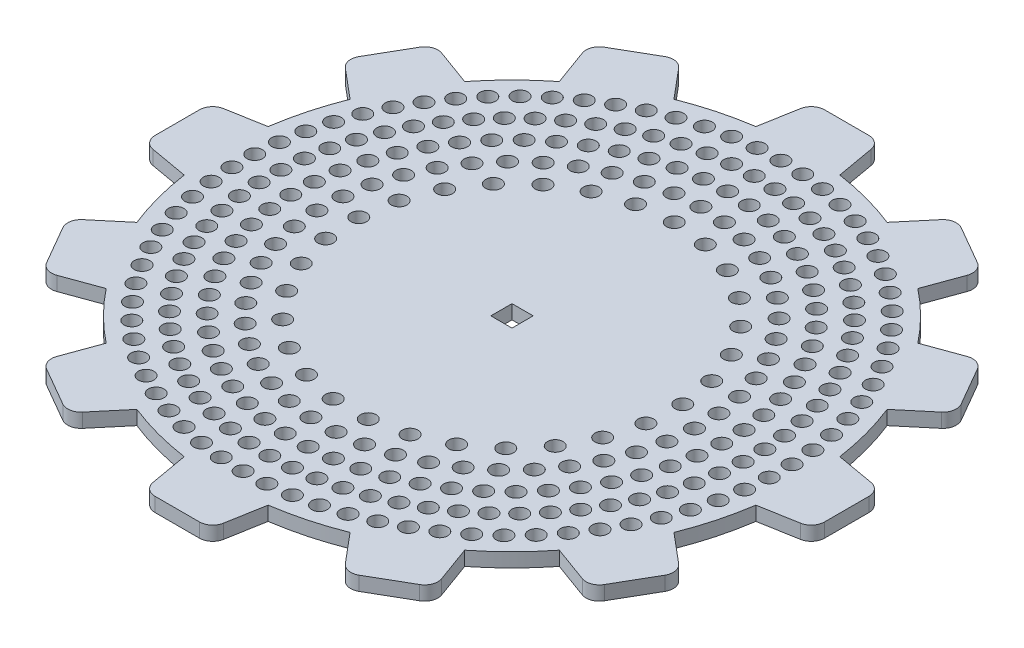
SolidWorks part; units mm, degrees
material "Balsa"
ref_plane "Front Plane" through (0, 0, 0) normal (0, 0, 1) x (1, 0, 0)
ref_plane "Top Plane" through (0, 0, 0) normal (0, 1, 0) x (1, 0, 0)
ref_plane "Right Plane" through (0, 0, 0) normal (1, 0, 0) x (0, 0, -1)
sketch "Sketch1" plane through (0, 0, 0) normal (0, 1, 0) x (1, 0, 0)
  line L0 (0, 85) -> (0, 73) construction
  line L1 (-4.7625, 4.7625) -> (4.7625, 4.7625)
  line L2 (-4.7625, 4.7625) -> (-4.7625, -4.7625)
  line L7 (-4.7625, -4.7625) -> (4.7625, -4.7625)
  line L8 (0, 121) -> (0, 109) construction
  line L9 (0, 109) -> (0, 97) construction
  line L10 (0, 97) -> (0, 85) construction
  line L11 (4.7625, 4.7625) -> (4.7625, -4.7625)
  line L12 (-4.7625, 4.7625) -> (4.7625, -4.7625) construction
  line L13 (-4.7625, -4.7625) -> (4.7625, 4.7625) construction
  circle A0 centre (0, 0) radius 130
  circle A39 centre (0, 85) radius 3.5
  circle A40 centre (0, 97) radius 3.5
  circle A41 centre (0, 109) radius 3.5
  circle A42 centre (0, 121) radius 3.5
  circle A43 centre (10.2615, 120.5641) radius 3.5
  circle A44 centre (20.4491, 119.2595) radius 3.5
  circle A45 centre (30.4893, 117.0957) radius 3.5
  circle A46 centre (40.3099, 114.0882) radius 3.5
  circle A47 centre (49.8401, 110.2586) radius 3.5
  circle A48 centre (59.0111, 105.6347) radius 3.5
  circle A49 centre (67.7569, 100.2497) radius 3.5
  circle A50 centre (76.0146, 94.1423) radius 3.5
  circle A51 centre (83.7246, 87.3567) radius 3.5
  circle A52 centre (90.8313, 79.9416) radius 3.5
  circle A53 centre (97.2837, 71.9506) radius 3.5
  circle A54 centre (103.035, 63.4412) radius 3.5
  circle A55 centre (108.044, 54.4747) radius 3.5
  circle A56 centre (112.2746, 45.1156) radius 3.5
  circle A57 centre (115.6962, 35.4316) radius 3.5
  circle A58 centre (118.2842, 25.4922) radius 3.5
  circle A59 centre (120.02, 15.3692) radius 3.5
  circle A60 centre (120.891, 5.1354) radius 3.5
  circle A61 centre (120.891, -5.1354) radius 3.5
  circle A62 centre (120.02, -15.3692) radius 3.5
  circle A63 centre (118.2842, -25.4922) radius 3.5
  circle A64 centre (115.6962, -35.4316) radius 3.5
  circle A65 centre (112.2746, -45.1156) radius 3.5
  circle A66 centre (108.044, -54.4747) radius 3.5
  circle A67 centre (103.035, -63.4412) radius 3.5
  circle A68 centre (97.2837, -71.9506) radius 3.5
  circle A69 centre (90.8313, -79.9416) radius 3.5
  circle A70 centre (83.7246, -87.3567) radius 3.5
  circle A71 centre (76.0146, -94.1423) radius 3.5
  circle A72 centre (67.7569, -100.2497) radius 3.5
  circle A73 centre (59.0111, -105.6347) radius 3.5
  circle A74 centre (49.8401, -110.2586) radius 3.5
  circle A75 centre (40.3099, -114.0882) radius 3.5
  circle A76 centre (30.4893, -117.0957) radius 3.5
  circle A77 centre (20.4491, -119.2595) radius 3.5
  circle A78 centre (10.2615, -120.5641) radius 3.5
  circle A79 centre (0, -121) radius 3.5
  circle A80 centre (-10.2615, -120.5641) radius 3.5
  circle A81 centre (-20.4491, -119.2595) radius 3.5
  circle A82 centre (-30.4893, -117.0957) radius 3.5
  circle A83 centre (-40.3099, -114.0882) radius 3.5
  circle A84 centre (-49.8401, -110.2586) radius 3.5
  circle A85 centre (-59.0111, -105.6347) radius 3.5
  circle A86 centre (-67.7569, -100.2497) radius 3.5
  circle A87 centre (-76.0146, -94.1423) radius 3.5
  circle A88 centre (-83.7246, -87.3567) radius 3.5
  circle A89 centre (-90.8313, -79.9416) radius 3.5
  circle A90 centre (-97.2837, -71.9506) radius 3.5
  circle A91 centre (-103.035, -63.4412) radius 3.5
  circle A92 centre (-108.044, -54.4747) radius 3.5
  circle A93 centre (-112.2746, -45.1156) radius 3.5
  circle A94 centre (-115.6962, -35.4316) radius 3.5
  circle A95 centre (-118.2842, -25.4922) radius 3.5
  circle A96 centre (-120.02, -15.3692) radius 3.5
  circle A97 centre (-120.891, -5.1354) radius 3.5
  circle A98 centre (-120.891, 5.1354) radius 3.5
  circle A99 centre (-120.02, 15.3692) radius 3.5
  circle A100 centre (-118.2842, 25.4922) radius 3.5
  circle A101 centre (-115.6962, 35.4316) radius 3.5
  circle A102 centre (-112.2746, 45.1156) radius 3.5
  circle A103 centre (-108.044, 54.4747) radius 3.5
  circle A104 centre (-103.035, 63.4412) radius 3.5
  circle A105 centre (-97.2837, 71.9506) radius 3.5
  circle A106 centre (-90.8313, 79.9416) radius 3.5
  circle A107 centre (-83.7246, 87.3567) radius 3.5
  circle A108 centre (9.7707, 108.5612) radius 3.5
  circle A109 centre (19.4627, 107.2483) radius 3.5
  circle A110 centre (28.998, 105.072) radius 3.5
  circle A111 centre (38.2999, 102.0496) radius 3.5
  circle A112 centre (47.2933, 98.2056) radius 3.5
  circle A113 centre (55.906, 93.5709) radius 3.5
  circle A114 centre (64.0686, 88.1829) radius 3.5
  circle A115 centre (71.7153, 82.0848) radius 3.5
  circle A116 centre (78.7846, 75.3258) radius 3.5
  circle A117 centre (85.2196, 67.9604) radius 3.5
  circle A118 centre (90.9685, 60.0478) radius 3.5
  circle A119 centre (95.9849, 51.6517) radius 3.5
  circle A120 centre (100.2285, 42.8397) radius 3.5
  circle A121 centre (103.6652, 33.6829) radius 3.5
  circle A122 centre (106.2671, 24.2548) radius 3.5
  circle A123 centre (108.0135, 14.6314) radius 3.5
  circle A124 centre (108.8902, 4.8903) radius 3.5
  circle A125 centre (108.8902, -4.8903) radius 3.5
  circle A126 centre (108.0135, -14.6314) radius 3.5
  circle A127 centre (106.2671, -24.2548) radius 3.5
  circle A128 centre (103.6652, -33.6829) radius 3.5
  circle A129 centre (100.2285, -42.8397) radius 3.5
  circle A130 centre (95.9849, -51.6517) radius 3.5
  circle A131 centre (90.9685, -60.0478) radius 3.5
  circle A132 centre (85.2196, -67.9604) radius 3.5
  circle A133 centre (78.7846, -75.3258) radius 3.5
  circle A134 centre (71.7153, -82.0848) radius 3.5
  circle A135 centre (64.0686, -88.1829) radius 3.5
  circle A136 centre (55.906, -93.5709) radius 3.5
  circle A137 centre (47.2933, -98.2056) radius 3.5
  circle A138 centre (38.2999, -102.0496) radius 3.5
  circle A139 centre (28.998, -105.072) radius 3.5
  circle A140 centre (19.4627, -107.2483) radius 3.5
  circle A141 centre (9.7707, -108.5612) radius 3.5
  circle A142 centre (0, -109) radius 3.5
  circle A143 centre (-9.7707, -108.5612) radius 3.5
  circle A144 centre (-19.4627, -107.2483) radius 3.5
  circle A145 centre (-28.998, -105.072) radius 3.5
  circle A146 centre (-38.2999, -102.0496) radius 3.5
  circle A147 centre (-47.2933, -98.2056) radius 3.5
  circle A148 centre (-55.906, -93.5709) radius 3.5
  circle A149 centre (-64.0686, -88.1829) radius 3.5
  circle A150 centre (-71.7153, -82.0848) radius 3.5
  circle A151 centre (-78.7846, -75.3258) radius 3.5
  circle A152 centre (-85.2196, -67.9604) radius 3.5
  circle A153 centre (-90.9685, -60.0478) radius 3.5
  circle A154 centre (-95.9849, -51.6517) radius 3.5
  circle A155 centre (-100.2285, -42.8397) radius 3.5
  circle A156 centre (-103.6652, -33.6829) radius 3.5
  circle A157 centre (-106.2671, -24.2548) radius 3.5
  circle A158 centre (-108.0135, -14.6314) radius 3.5
  circle A159 centre (-108.8902, -4.8903) radius 3.5
  circle A160 centre (-108.8902, 4.8903) radius 3.5
  circle A161 centre (-108.0135, 14.6314) radius 3.5
  circle A162 centre (10.3105, 96.4505) radius 3.5
  circle A163 centre (20.5041, 94.8081) radius 3.5
  circle A164 centre (30.4654, 92.0916) radius 3.5
  circle A165 centre (40.0816, 88.3316) radius 3.5
  circle A166 centre (49.2436, 83.5707) radius 3.5
  circle A167 centre (57.8476, 77.863) radius 3.5
  circle A168 centre (65.7962, 71.2731) radius 3.5
  circle A169 centre (72.9994, 63.8756) radius 3.5
  circle A170 centre (79.3754, 55.7544) radius 3.5
  circle A171 centre (84.852, 47.0014) radius 3.5
  circle A172 centre (89.3673, 37.7159) radius 3.5
  circle A173 centre (92.8699, 28.0031) radius 3.5
  circle A174 centre (95.3204, 17.973) radius 3.5
  circle A175 centre (96.6908, 7.7393) radius 3.5
  circle A176 centre (96.9656, -2.5822) radius 3.5
  circle A177 centre (96.1418, -12.8744) radius 3.5
  circle A178 centre (94.2287, -23.0207) radius 3.5
  circle A179 centre (91.2479, -32.9062) radius 3.5
  circle A180 centre (87.2333, -42.4188) radius 3.5
  circle A181 centre (82.2302, -51.4508) radius 3.5
  circle A182 centre (76.2955, -59.8999) radius 3.5
  circle A183 centre (69.4963, -67.6703) radius 3.5
  circle A184 centre (61.9097, -74.6739) radius 3.5
  circle A185 centre (53.6216, -80.8315) radius 3.5
  circle A186 centre (44.726, -86.0732) radius 3.5
  circle A187 centre (35.3236, -90.3396) radius 3.5
  circle A188 centre (25.5209, -93.5825) radius 3.5
  circle A189 centre (15.4292, -95.765) radius 3.5
  circle A190 centre (5.1626, -96.8625) radius 3.5
  circle A191 centre (-5.1626, -96.8625) radius 3.5
  circle A192 centre (-15.4292, -95.765) radius 3.5
  circle A193 centre (-25.5209, -93.5825) radius 3.5
  circle A194 centre (-35.3236, -90.3396) radius 3.5
  circle A195 centre (-44.726, -86.0732) radius 3.5
  circle A196 centre (-53.6216, -80.8315) radius 3.5
  circle A197 centre (-61.9097, -74.6739) radius 3.5
  circle A198 centre (-69.4963, -67.6703) radius 3.5
  circle A199 centre (-76.2955, -59.8999) radius 3.5
  circle A200 centre (-82.2302, -51.4508) radius 3.5
  circle A201 centre (-87.2333, -42.4188) radius 3.5
  circle A202 centre (-91.2479, -32.9062) radius 3.5
  circle A203 centre (-94.2287, -23.0207) radius 3.5
  circle A204 centre (-96.1418, -12.8744) radius 3.5
  circle A205 centre (-96.9656, -2.5822) radius 3.5
  circle A206 centre (-96.6908, 7.7393) radius 3.5
  circle A207 centre (-95.3204, 17.973) radius 3.5
  circle A208 centre (-92.8699, 28.0031) radius 3.5
  circle A209 centre (-89.3673, 37.7159) radius 3.5
  circle A210 centre (-84.852, 47.0014) radius 3.5
  circle A211 centre (-79.3754, 55.7544) radius 3.5
  circle A212 centre (-72.9994, 63.8756) radius 3.5
  circle A214 centre (11.3294, 84.2416) radius 3.5
  circle A215 centre (22.4566, 81.9799) radius 3.5
  circle A216 centre (33.1831, 78.2552) radius 3.5
  circle A217 centre (43.3174, 73.1341) radius 3.5
  circle A218 centre (52.6787, 66.7079) radius 3.5
  circle A219 centre (61.1, 59.0914) radius 3.5
  circle A220 centre (68.431, 50.4203) radius 3.5
  circle A221 centre (74.5407, 40.8494) radius 3.5
  circle A222 centre (79.3204, 30.5497) radius 3.5
  circle A223 centre (82.6845, 19.7047) radius 3.5
  circle A224 centre (84.5731, 8.5081) radius 3.5
  circle A225 centre (84.9525, -2.8403) radius 3.5
  circle A226 centre (83.816, -14.138) radius 3.5
  circle A227 centre (81.1837, -25.1834) radius 3.5
  circle A228 centre (77.1027, -35.7795) radius 3.5
  circle A229 centre (71.6458, -45.737) radius 3.5
  circle A230 centre (64.9104, -54.8784) radius 3.5
  circle A231 centre (57.0167, -63.0404) radius 3.5
  circle A232 centre (48.1055, -70.0775) radius 3.5
  circle A233 centre (38.3359, -75.8641) radius 3.5
  circle A234 centre (27.8821, -80.2969) radius 3.5
  circle A235 centre (16.9308, -83.2967) radius 3.5
  circle A236 centre (5.6774, -84.8102) radius 3.5
  circle A237 centre (-5.6774, -84.8102) radius 3.5
  circle A238 centre (-16.9308, -83.2967) radius 3.5
  circle A239 centre (-27.8821, -80.2969) radius 3.5
  circle A240 centre (-38.3359, -75.8641) radius 3.5
  circle A241 centre (-48.1055, -70.0775) radius 3.5
  circle A242 centre (-57.0167, -63.0404) radius 3.5
  circle A243 centre (-64.9104, -54.8784) radius 3.5
  circle A244 centre (-71.6458, -45.737) radius 3.5
  circle A245 centre (-77.1027, -35.7795) radius 3.5
  circle A246 centre (-81.1837, -25.1834) radius 3.5
  circle A247 centre (-83.816, -14.138) radius 3.5
  circle A248 centre (-84.9525, -2.8403) radius 3.5
  circle A249 centre (-84.5731, 8.5081) radius 3.5
  circle A250 centre (-82.6845, 19.7047) radius 3.5
  circle A251 centre (-79.3204, 30.5497) radius 3.5
  circle A252 centre (-74.5407, 40.8494) radius 3.5
  circle A253 centre (-68.431, 50.4203) radius 3.5
  circle A254 centre (-61.1, 59.0914) radius 3.5
  circle A255 centre (-52.6787, 66.7079) radius 3.5
  circle A256 centre (-43.3174, 73.1341) radius 3.5
  circle A257 centre (-33.1831, 78.2552) radius 3.5
  circle A258 centre (-22.4566, 81.9799) radius 3.5
  circle A259 centre (-11.3294, 84.2416) radius 3.5
  circle A260 centre (-65.7962, 71.2731) radius 3.5
  circle A261 centre (-57.8476, 77.863) radius 3.5
  circle A262 centre (-49.2436, 83.5707) radius 3.5
  circle A263 centre (-40.0816, 88.3316) radius 3.5
  circle A264 centre (-30.4654, 92.0916) radius 3.5
  circle A265 centre (-20.5041, 94.8081) radius 3.5
  circle A266 centre (-10.3105, 96.4505) radius 3.5
  circle A267 centre (-106.2671, 24.2548) radius 3.5
  circle A268 centre (-103.6652, 33.6829) radius 3.5
  circle A269 centre (-100.2285, 42.8397) radius 3.5
  circle A270 centre (-95.9849, 51.6517) radius 3.5
  circle A271 centre (-90.9685, 60.0478) radius 3.5
  circle A272 centre (-85.2196, 67.9604) radius 3.5
  circle A273 centre (-78.7846, 75.3258) radius 3.5
  circle A274 centre (-71.7153, 82.0848) radius 3.5
  circle A275 centre (-64.0686, 88.1829) radius 3.5
  circle A276 centre (-55.906, 93.5709) radius 3.5
  circle A277 centre (-47.2933, 98.2056) radius 3.5
  circle A278 centre (-38.2999, 102.0496) radius 3.5
  circle A279 centre (-28.998, 105.072) radius 3.5
  circle A280 centre (-19.4627, 107.2483) radius 3.5
  circle A281 centre (-9.7707, 108.5612) radius 3.5
  circle A282 centre (-76.0146, 94.1423) radius 3.5
  circle A283 centre (-67.7569, 100.2497) radius 3.5
  circle A284 centre (-59.0111, 105.6347) radius 3.5
  circle A285 centre (-49.8401, 110.2586) radius 3.5
  circle A286 centre (-40.3099, 114.0882) radius 3.5
  circle A287 centre (-30.4893, 117.0957) radius 3.5
  circle A288 centre (-20.4491, 119.2595) radius 3.5
  circle A289 centre (-10.2615, 120.5641) radius 3.5
  circle A290 centre (0, 73) radius 3.5
  circle A291 centre (15.6928, 71.2933) radius 3.5
  circle A292 centre (30.6519, 66.253) radius 3.5
  circle A293 centre (44.1777, 58.1148) radius 3.5
  circle A294 centre (55.6378, 47.2592) radius 3.5
  circle A295 centre (64.4964, 34.1938) radius 3.5
  circle A296 centre (70.3391, 19.5296) radius 3.5
  circle A297 centre (72.8929, 3.9521) radius 3.5
  circle A298 centre (72.0383, -11.8101) radius 3.5
  circle A299 centre (67.8153, -27.0201) radius 3.5
  circle A300 centre (60.4213, -40.9667) radius 3.5
  circle A301 centre (50.2021, -52.9977) radius 3.5
  circle A302 centre (37.6354, -62.5506) radius 3.5
  circle A303 centre (23.309, -69.1787) radius 3.5
  circle A304 centre (7.8927, -72.5721) radius 3.5
  circle A305 centre (-7.8927, -72.5721) radius 3.5
  circle A306 centre (-23.309, -69.1787) radius 3.5
  circle A307 centre (-37.6354, -62.5506) radius 3.5
  circle A308 centre (-50.2021, -52.9977) radius 3.5
  circle A309 centre (-60.4213, -40.9667) radius 3.5
  circle A310 centre (-67.8153, -27.0201) radius 3.5
  circle A311 centre (-72.0383, -11.8101) radius 3.5
  circle A312 centre (-72.8929, 3.9521) radius 3.5
  circle A313 centre (-70.3391, 19.5296) radius 3.5
  circle A314 centre (-64.4964, 34.1938) radius 3.5
  circle A315 centre (-55.6378, 47.2592) radius 3.5
  circle A316 centre (-44.1777, 58.1148) radius 3.5
  circle A317 centre (-30.6519, 66.253) radius 3.5
  circle A318 centre (-15.6928, 71.2933) radius 3.5
  point P568 (0, 0)
  dimension "D2" = 12
  dimension "D3" = 260
  dimension "D4" = 85
  dimension "D12" = 7
  dimension "D5" = 9.525
  dimension "D8" = 74
  dimension "D9" = 70
  dimension "D10" = 59
  dimension "D11" = 47
  dimension "D6" = 29
extrude "Boss-Extrude1" add sketch "Sketch1" along normal blind 6.35
sketch "Sketch2" plane through (0, 6.35, 0) normal (0, 1, 0) x (1, 0, 0)
  line L0 (0, 0) -> (0, 202.4314) construction
  line L1 (0, 0) -> (-221.3243, 0) construction
  line L2 (0, 0) -> (223.2936, 0) construction
  line L3 (0, 150.6218) -> (15, 150.6218)
  line L4 (0, 150.6218) -> (-15, 150.6218)
  line L5 (-15, 150.6218) -> (-18.8792, 128.6218)
  line L6 (15, 150.6218) -> (18.8792, 128.6218)
  line L7 (62.3205, 137.9423) -> (47.9611, 120.8294)
  line L8 (75.3109, 130.4423) -> (88.3013, 122.9423)
  line L9 (75.3109, 130.4423) -> (62.3205, 137.9423)
  line L10 (88.3013, 122.9423) -> (80.6608, 101.9502)
  line L11 (122.9423, 88.3013) -> (101.9502, 80.6608)
  line L12 (130.4423, 75.3109) -> (137.9423, 62.3205)
  line L13 (130.4423, 75.3109) -> (122.9423, 88.3013)
  line L14 (137.9423, 62.3205) -> (120.8294, 47.9611)
  line L15 (150.6218, 15) -> (128.6218, 18.8792)
  line L16 (150.6218, 0) -> (150.6218, -15)
  line L17 (150.6218, 0) -> (150.6218, 15)
  line L18 (150.6218, -15) -> (128.6218, -18.8792)
  line L19 (137.9423, -62.3205) -> (120.8294, -47.9611)
  line L20 (130.4423, -75.3109) -> (122.9423, -88.3013)
  line L21 (130.4423, -75.3109) -> (137.9423, -62.3205)
  line L22 (122.9423, -88.3013) -> (101.9502, -80.6608)
  line L23 (88.3013, -122.9423) -> (80.6608, -101.9502)
  line L24 (75.3109, -130.4423) -> (62.3205, -137.9423)
  line L25 (75.3109, -130.4423) -> (88.3013, -122.9423)
  line L26 (62.3205, -137.9423) -> (47.9611, -120.8294)
  line L27 (15, -150.6218) -> (18.8792, -128.6218)
  line L28 (0, -150.6218) -> (-15, -150.6218)
  line L29 (0, -150.6218) -> (15, -150.6218)
  line L30 (-15, -150.6218) -> (-18.8792, -128.6218)
  line L31 (-62.3205, -137.9423) -> (-47.9611, -120.8294)
  line L32 (-75.3109, -130.4423) -> (-88.3013, -122.9423)
  line L33 (-75.3109, -130.4423) -> (-62.3205, -137.9423)
  line L34 (-88.3013, -122.9423) -> (-80.6608, -101.9502)
  line L35 (-122.9423, -88.3013) -> (-101.9502, -80.6608)
  line L36 (-130.4423, -75.3109) -> (-137.9423, -62.3205)
  line L37 (-130.4423, -75.3109) -> (-122.9423, -88.3013)
  line L38 (-137.9423, -62.3205) -> (-120.8294, -47.9611)
  line L39 (-150.6218, -15) -> (-128.6218, -18.8792)
  line L40 (-150.6218, 0) -> (-150.6218, 15)
  line L41 (-150.6218, 0) -> (-150.6218, -15)
  line L42 (-150.6218, 15) -> (-128.6218, 18.8792)
  line L43 (-137.9423, 62.3205) -> (-120.8294, 47.9611)
  line L44 (-130.4423, 75.3109) -> (-122.9423, 88.3013)
  line L45 (-130.4423, 75.3109) -> (-137.9423, 62.3205)
  line L46 (-122.9423, 88.3013) -> (-101.9502, 80.6608)
  line L47 (-88.3013, 122.9423) -> (-80.6608, 101.9502)
  line L48 (-75.3109, 130.4423) -> (-62.3205, 137.9423)
  line L49 (-75.3109, 130.4423) -> (-88.3013, 122.9423)
  line L50 (-62.3205, 137.9423) -> (-47.9611, 120.8294)
  arc A0 (18.8792, 128.6218) -> (-18.8792, 128.6218) centre (0, 0) ccw
  circle A1 centre (0, 0) radius 130 construction
  arc A2 (80.6608, 101.9502) -> (47.9611, 120.8294) centre (0, 0) ccw
  arc A3 (120.8294, 47.9611) -> (101.9502, 80.6608) centre (0, 0) ccw
  arc A4 (128.6218, -18.8792) -> (128.6218, 18.8792) centre (0, 0) ccw
  arc A5 (101.9502, -80.6608) -> (120.8294, -47.9611) centre (0, 0) ccw
  arc A6 (47.9611, -120.8294) -> (80.6608, -101.9502) centre (0, 0) ccw
  arc A7 (-18.8792, -128.6218) -> (18.8792, -128.6218) centre (0, 0) ccw
  arc A8 (-80.6608, -101.9502) -> (-47.9611, -120.8294) centre (0, 0) ccw
  arc A9 (-120.8294, -47.9611) -> (-101.9502, -80.6608) centre (0, 0) ccw
  arc A10 (-128.6218, 18.8792) -> (-128.6218, -18.8792) centre (0, 0) ccw
  arc A11 (-101.9502, 80.6608) -> (-120.8294, 47.9611) centre (0, 0) ccw
  arc A12 (-47.9611, 120.8294) -> (-80.6608, 101.9502) centre (0, 0) ccw
  point P70 (0, 0)
  dimension "D1" = 100
  dimension "D2" = 100
  dimension "D3" = 15
  dimension "D4" = 22
  dimension "D5" = 12
extrude "Boss-Extrude2" add sketch "Sketch2" against normal up to surface (6.35 mm away) up to face at (-33.1831, 0, -74.7552)
fillet "Fillet3" radius 6 23 edges at (88.3013, 3.175, -122.9423) (62.3205, 3.175, -137.9423) (137.9423, 3.175, -62.3205) (150.6218, 3.175, -15) (150.6218, 3.175, 15) (137.9423, 3.175, 62.3205) (122.9423, 3.175, 88.3013) (88.3013, 3.175, 122.9423) (62.3205, 3.175, 137.9423) (15, 3.175, 150.6218) (-15, 3.175, 150.6218) (-62.3205, 3.175, 137.9423) (-88.3013, 3.175, 122.9423) (-122.9423, 3.175, 88.3013) (-137.9423, 3.175, 62.3205) (-150.6218, 3.175, 15) (15, 3.175, -150.6218) (-15, 3.175, -150.6218) (-62.3205, 3.175, -137.9423) (-88.3013, 3.175, -122.9423) (-122.9423, 3.175, -88.3013) (-137.9423, 3.175, -62.3205) (-150.6218, 3.175, -15)
fillet "Fillet4" radius 6 1 edges at (122.9423, 3.175, -88.3013)
sketch "Sketch3" plane through (0, 6.35, 0) normal (0, 1, 0) x (1, 0, 0)
  circle A0 centre (0, 0) radius 50 construction
  circle A1 centre (0, 0) radius 37.5 construction
  text T0 "PARTHENOPE  |  WPI MUSICAL ROBOTICS A18  |  MATTHEW BISSON, JORDAN GROTZ, CESAR GUERRERO, MICHAEL SIDLER  |  "
  text T1 "DISK 3  |  10RPS  |  D4 (29 holes)  |  Bb4 (47 holes)  |  D5 (59 holes)  |  F5 (70 holes)  |  F#5 (74 holes)  |  "
  dimension "D1" = 100
  dimension "D2" = 75
